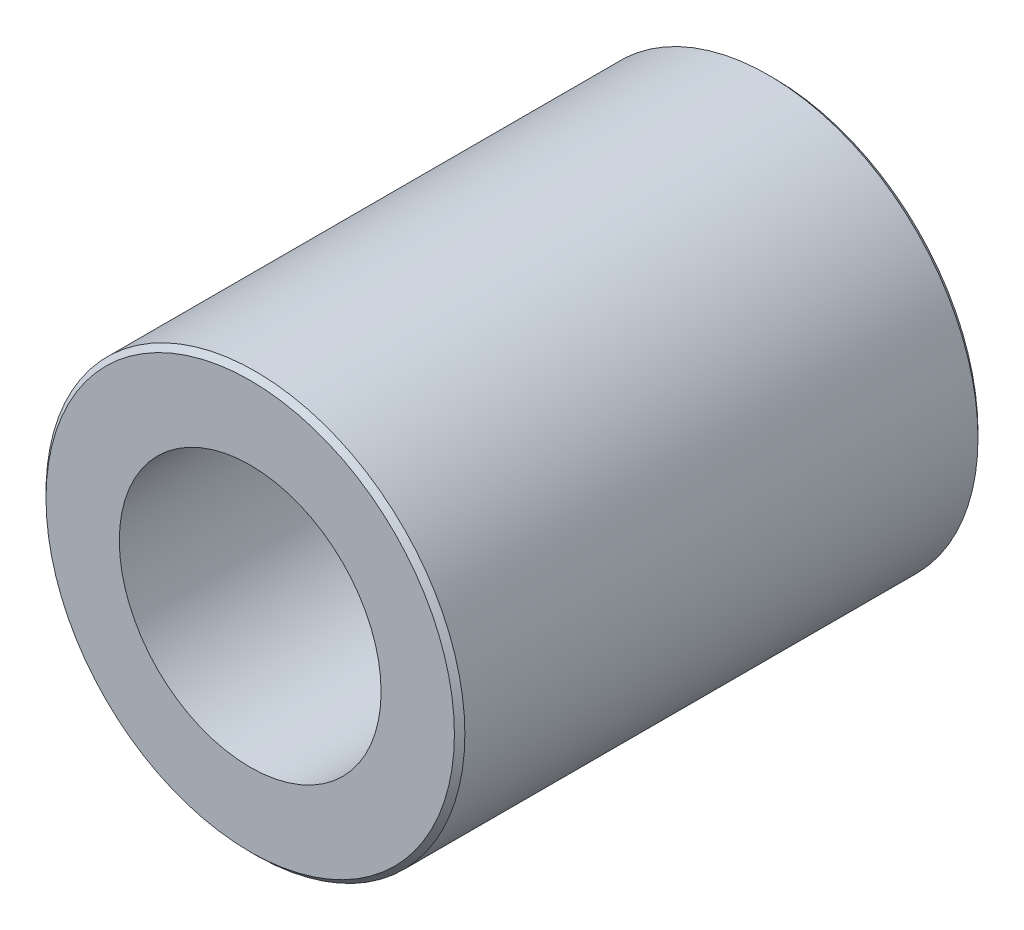
SolidWorks part; units mm, degrees
material "Laiton"
ref_plane "Plan de face" through (0, 0, 0) normal (0, 0, 1) x (1, 0, 0)
ref_plane "Plan de dessus" through (0, 0, 0) normal (0, 1, 0) x (1, 0, 0)
ref_plane "Plan de droite" through (0, 0, 0) normal (1, 0, 0) x (0, 0, -1)
sketch "Esquisse1" plane through (0, 0, 0) normal (0, 0, 1) x (1, 0, 0)
  circle A0 centre (0, 0) radius 2
  circle A1 centre (0, 0) radius 1.06
  dimension "D1" = 4
  dimension "D2" = 2.12
extrude "Extrusion1" add sketch "Esquisse1" along normal blind 5
ref_axis "Taraudage1-Axe" through (0, 0, 5) along (0, 0, -1)
ref_plane "Taraudage1-PlanEnBout" through (0, 0, 5) normal (0, 0, 1) x (1, 0, 0)
sketch "Esquisse2" plane through (0, 0, 5) normal (0, 0, 1) x (1, 0, 0)
  circle A0 centre (0, 0) radius 1.06
  dimension "D1" = 2.12
curve "Hélice/Spirale1" pitch 0.35 height 5 turns 14.2857
ref_plane "Taraudage1-PlanTransversal" through (0.918, 0.53, 5) normal (-0.5, 0.866, 0) x (-0.866, -0.5, 0)
sketch "Esquisse3" plane through (0.918, 0.53, 5) normal (-0.5, 0.866, 0) x (-0.866, -0.5, 0)
  line L0 (0, 0) -> (0.021, 0) construction
  line L1 (0.021, 0.1434) -> (0.021, -0.1434)
  line L2 (0.021, -0.1434) -> (-0.2019, -0.0147)
  line L3 (-0.2019, -0.0147) -> (-0.2019, 0.0147)
  line L4 (0.021, 0.1434) -> (-0.2019, 0.0147)
  line L6 (1.06, 0) -> (1.06, -4) construction
  point P6 (-0.2019, 0)
  dimension "D1" = 0.021
  dimension "D2" = 0.1434
  dimension "D3" = 120
  dimension "D4" = 0.2229
  dimension "D5" = 90
sweep "Enlèvement de matière-Balayage1" [suppressed] cut profiles "Esquisse3" path "Hélice/Spirale1"
sketch "Esquisse4" plane through (0, 0, 5) normal (0, 0, 1) x (1, 0, 0)
  circle A1 centre (0, 0) radius 1.06
  circle A2 centre (0, 0) radius 1.06
  dimension "D1" = 0
curve "Hélice/Spirale2" [suppressed] pitch 0.35 height 0.175 turns 0.5
sketch "Esquisse5" plane through (0.918, 0.53, 5) normal (-0.5, 0.866, 0) x (-0.866, -0.5, 0)
  line L4 (0.021, -0.1434) -> (0.021, 0.1434)
  line L5 (-0.2019, -0.0147) -> (0.021, -0.1434)
  line L6 (-0.2019, 0.0147) -> (-0.2019, -0.0147)
  line L7 (0.021, 0.1434) -> (-0.2019, 0.0147)
  line L8 (0.021, -0.1434) -> (0.021, 0.1434)
  line L9 (-0.2019, -0.0147) -> (0.021, -0.1434)
  line L10 (-0.2019, 0.0147) -> (-0.2019, -0.0147)
  line L11 (0.021, 0.1434) -> (-0.2019, 0.0147)
  dimension "D1" = 0
sweep "Enlèvement de matière-Balayage2" [suppressed] cut profiles "Esquisse5" path "Hélice/Spirale2"
chamfer "Chanfrein1" distance 0.05 angle 45 2 edges at (2, 0, 0) (2, 0, 5)
other "SupprimerFace1" face at (1.06, 0, 5) and patch yes
hole_wizard "Trou taraudé M31" positions "Esquisse8" profile "Esquisse9" tap size "M3" standard "ISO" end condition up to next
sketch "Esquisse8" plane through (0, 0, 0) normal (0, 0, -1) x (-1, 0, 0)
  point P0 (0, 0)
sketch "Esquisse9" plane through (0, 0, 0) normal (1, 0, 0) x (0, 1, 0)
  line L0 (0, 0) -> (0, 5)
  line L1 (0, 5) -> (1.25, 5)
  line L2 (1.25, 5) -> (1.25, 0)
  line L5 (1.25, 0) -> (0, 0)
  line L11 (0, -6.35) -> (0, 107.95) construction
  dimension "Diamètre du trou pour taraudage jusqu'au prochain" = 2.5
  dimension "Profondeur du trou pour taraudage jusqu'au prochain" = 5
cosmetic thread "Filetage de perçage1" parameters "D2"=3
